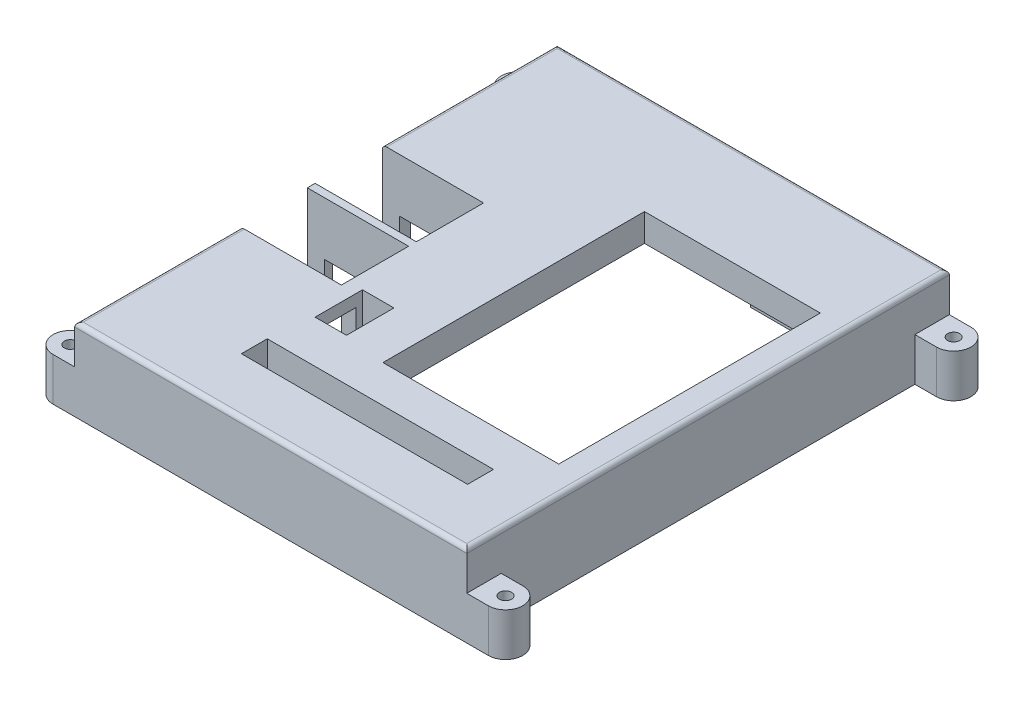
SolidWorks part; units mm, degrees
ref_plane "Front Plane" through (0, 0, 0) normal (0, 0, 1) x (1, 0, 0)
ref_plane "Top Plane" through (0, 0, 0) normal (0, 1, 0) x (1, 0, 0)
ref_plane "Right Plane" through (0, 0, 0) normal (1, 0, 0) x (0, 0, -1)
sketch "Sketch1" plane through (0, 0, 0) normal (0, 1, 0) x (1, 0, 0)
  line L0 (0, 56) -> (0, -56) construction
  line L1 (-39.5, 50) -> (39.5, 50) construction
  line L2 (-39.5, 50) -> (-39.5, -50) construction
  line L3 (-39.5, -50) -> (39.5, -50) construction
  line L4 (39.5, 50) -> (39.5, -50) construction
  line L5 (-45.5, 56) -> (45.5, 56)
  line L6 (-45.5, 56) -> (-45.5, -56)
  line L7 (-45.5, -56) -> (45.5, -56)
  line L8 (45.5, 56) -> (45.5, -56)
  point P4 (-39.5, 0)
  point P6 (0, 50)
  dimension "D1" = 100
  dimension "D2" = 79
  dimension "D3" = 112
  dimension "D4" = 91
extrude "Base" add sketch "Sketch1" along normal blind 19
sketch "Sketch2" plane through (0, 0, 0) normal (0, 1, 0) x (1, 0, 0)
  line L0 (-45.5, 56) -> (-50.5, 56)
  line L1 (-45.5, 56) -> (-45.5, 48)
  line L2 (-45.5, 56) -> (-45.5, -56) construction
  line L3 (-45.5, 48) -> (-50.5, 48)
  line L6 (0, 56) -> (0, -56) construction
  line L7 (45.5, 56) -> (-45.5, 56) construction
  line L8 (-45.5, -56) -> (45.5, -56) construction
  line L9 (-45.5, 0) -> (45.5, 0) construction
  line L10 (45.5, -56) -> (45.5, 56) construction
  line L11 (45.5, 48) -> (50.5, 48)
  line L12 (45.5, 56) -> (45.5, 48)
  line L13 (45.5, 56) -> (50.5, 56)
  line L14 (45.5, -56) -> (50.5, -56)
  line L15 (45.5, -56) -> (45.5, -48)
  line L16 (45.5, -48) -> (50.5, -48)
  line L17 (-45.5, -48) -> (-50.5, -48)
  line L18 (-45.5, -56) -> (-45.5, -48)
  line L19 (-45.5, -56) -> (-50.5, -56)
  arc A0 (-50.5, 48) -> (-50.5, 56) centre (-50.5, 52) cw
  circle A1 centre (-50.5, 52) radius 1.4
  circle A2 centre (50.5, 52) radius 1.4
  arc A3 (50.5, 48) -> (50.5, 56) centre (50.5, 52) ccw
  arc A4 (50.5, -48) -> (50.5, -56) centre (50.5, -52) cw
  circle A5 centre (50.5, -52) radius 1.4
  circle A6 centre (-50.5, -52) radius 1.4
  arc A7 (-50.5, -48) -> (-50.5, -56) centre (-50.5, -52) ccw
  dimension "D2" = 2.8
  dimension "D1" = 8
  dimension "D3" = 5
extrude "Case Assembly Holes" add sketch "Sketch2" along normal blind 10
sketch "Sketch3" plane through (0, 0, 0) normal (0, -1, 0) x (1, 0, 0)
  line L1 (41.5, -52) -> (-41.5, -52)
  line L2 (41.5, -52) -> (41.5, 52)
  line L3 (41.5, 52) -> (-41.5, 52)
  line L4 (-41.5, -52) -> (-41.5, 52)
  line L5 (41.5, -52) -> (-41.5, 52) construction
  line L6 (41.5, 52) -> (-41.5, -52) construction
  point P0 (0, 0)
  dimension "D1" = 83
  dimension "D2" = 104
extrude "Module Cutout" cut sketch "Sketch3" against normal blind 6.6
sketch "Sketch4" plane through (-45.5, 0, 0) normal (-1, 0, 0) x (0, 0, 1)
  line L0 (-50, 0) -> (50, 0) construction
  line L1 (-48, 0) -> (48, 0) construction
  line L3 (-49.25, 0) -> (-38.75, 0)
  line L4 (-49.25, 0) -> (-49.25, 6)
  line L5 (-49.25, 6) -> (-38.75, 6)
  line L6 (-38.75, 0) -> (-38.75, 6)
  line L7 (47, 0) -> (37, 0)
  line L8 (47, 0) -> (47, 6)
  line L9 (47, 6) -> (37, 6)
  line L10 (37, 0) -> (37, 6)
  dimension "D1" = 100
  dimension "D2" = 6
  dimension "D3" = 10.5
  dimension "D4" = 0.75
  dimension "D5" = 10
  dimension "D6" = 3
extrude "USB-C and Micro-USB Slots" cut sketch "Sketch4" against normal blind 7 and the other way through all
sketch "Sketch5" plane through (-45.5, 0, 0) normal (-1, 0, 0) x (0, 0, 1)
  line L0 (-38.75, 0) -> (37, 0) construction
  line L1 (-34.5, 0) -> (-18, 0)
  line L2 (-34.5, 0) -> (-34.5, 10)
  line L3 (-34.5, 10) -> (-18, 10)
  line L4 (-18, 0) -> (-18, 10)
  line L5 (-50, 0) -> (50, 0) construction
  line L6 (1.1, 19) -> (1.1, 0) construction
  line L7 (-15.4, 0) -> (0.2, 0)
  line L8 (-15.4, 0) -> (-15.4, 19)
  line L9 (-15.4, 19) -> (0.2, 19)
  line L10 (0.2, 0) -> (0.2, 19)
  line L11 (-56, 19) -> (56, 19) construction
  line L12 (17.6, 19) -> (2, 19)
  line L13 (2, 0) -> (2, 19)
  line L14 (17.6, 0) -> (2, 0)
  line L15 (17.6, 0) -> (17.6, 19)
  point P10 (0, 0)
  point P21 (-7.6, 0)
  dimension "D1" = 100
  dimension "D2" = 15.5
  dimension "D3" = 16.5
  dimension "D4" = 10
  dimension "D5" = 34.6
  dimension "D6" = 15.6
  dimension "D7" = 19
  dimension "D8" = 8.7
extrude "HDMI and USB Slots" cut sketch "Sketch5" against normal blind 23.5
sketch "Sketch6" plane through (-45.5, 0, 0) normal (-1, 0, 0) x (0, 0, 1)
  line L0 (-50, 0) -> (50, 0) construction
  line L1 (-52, 0) -> (52, 0) construction
  line L3 (35.5, 0) -> (17.6, 0)
  line L4 (35.5, 0) -> (35.5, 16.2)
  line L5 (35.5, 16.2) -> (17.6, 16.2)
  line L6 (17.6, 0) -> (17.6, 16.2)
  line L7 (17.6, 0) -> (17.6, 19) construction
  point P4 (0, 0)
  dimension "D1" = 100
  dimension "D3" = 16.2
  dimension "D4" = 14.5
extrude "Ethernet Slot" cut sketch "Sketch6" against normal blind 27
sketch "Sketch7" plane through (0, 6.6, 0) normal (0, -1, 0) x (1, 0, 0)
  line L1 (-39.5, 50) -> (39.5, 50) construction
  line L2 (-39.5, 50) -> (-39.5, -50) construction
  line L3 (-39.5, -50) -> (39.5, -50) construction
  line L4 (39.5, 50) -> (39.5, -50) construction
  line L5 (-5.5, -43.75) -> (18.5, -43.75)
  line L6 (-5.5, -43.75) -> (-5.5, -48.75)
  line L7 (-5.5, -48.75) -> (18.5, -48.75)
  line L8 (18.5, -43.75) -> (18.5, -48.75)
  line L9 (17.5, 33.8) -> (42.5, 33.8)
  line L11 (17.5, -37.8) -> (42.5, -37.8)
  line L12 (42.5, 33.8) -> (42.5, -37.8)
  line L13 (41.5, -52) -> (41.5, 52) construction
  line L14 (17.5, -37.8) -> (17.5, -41.8)
  line L15 (17.5, -41.8) -> (-11.5, -41.8)
  line L16 (17.5, 33.8) -> (17.5, 37.8)
  line L17 (17.5, 37.8) -> (-11.5, 37.8)
  line L18 (-11.5, 37.8) -> (-11.5, -41.8)
  circle A0 centre (-20.05, -12.75) radius 3.6
  circle A1 centre (-15.25, 32.09) radius 3.6
  point P6 (0, -50)
  point P8 (-39.5, 0)
  dimension "D1" = 7.2
  dimension "D4" = 19.45
  dimension "D5" = 37.25
  dimension "D6" = 24.25
  dimension "D7" = 17.91
  dimension "D2" = 79
  dimension "D3" = 100
  dimension "D8" = 24
  dimension "D9" = 5
  dimension "D10" = 1.25
  dimension "D11" = 21
  dimension "D12" = 71.6
  dimension "D13" = 25
  dimension "D14" = 12.2
  dimension "D15" = 1
  dimension "D16" = 4
  dimension "D17" = 29
extrude "Tall Components Cutouts" cut sketch "Sketch7" against normal blind 6
sketch "Sketch8" plane through (0, 19, 0) normal (0, 1, 0) x (1, 0, 0)
  line L0 (-45.5, -56) -> (45.5, -56) construction
  line L1 (-1.6, 32.35) -> (39.2, 32.35)
  line L2 (-1.6, 32.35) -> (-1.6, -28.35)
  line L3 (-1.6, -28.35) -> (39.2, -28.35)
  line L4 (39.2, 32.35) -> (39.2, -28.35)
  line L5 (45.5, -56) -> (45.5, 56) construction
  line L8 (32.7, -37) -> (-19.8, -37)
  line L9 (32.7, -37) -> (32.7, -43)
  line L10 (32.7, -43) -> (-19.8, -43)
  line L11 (-19.8, -37) -> (-19.8, -43)
  line L12 (-18.6, -16.1) -> (-11.3, -16.1)
  line L13 (-18.6, -16.1) -> (-18.6, -27.1)
  line L14 (-18.6, -27.1) -> (-11.3, -27.1)
  line L15 (-11.3, -16.1) -> (-11.3, -27.1)
  dimension "D1" = 40.8
  dimension "D2" = 60.7
  dimension "D3" = 27.65
  dimension "D4" = 6.3
  dimension "D5" = 6
  dimension "D6" = 52.5
  dimension "D7" = 12.8
  dimension "D8" = 13
  dimension "D9" = 11
  dimension "D10" = 7.3
  dimension "D11" = 28.9
  dimension "D12" = 56.8
extrude "Case Openings" cut sketch "Sketch8" against normal up to next
fillet "1mm Edge Fillets" radius 1 5 edges at (-45.5, 19, 36.8) (0, 19, 56) (45.5, 19, 0) (-45.5, 19, -35.7) (0, 19, -56)
